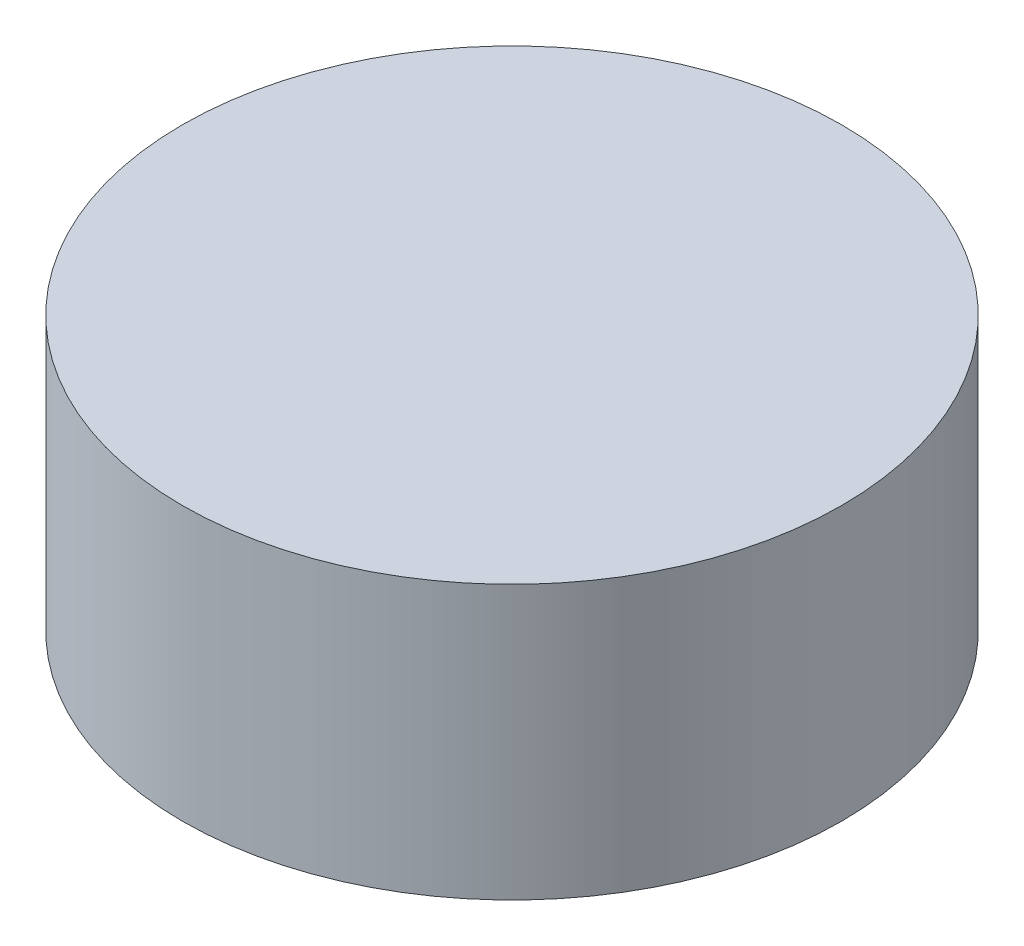
SolidWorks part; units mm, degrees
ref_plane "Front Plane" through (0, 0, 0) normal (0, 0, 1) x (1, 0, 0)
ref_plane "Top Plane" through (0, 0, 0) normal (0, 1, 0) x (1, 0, 0)
ref_plane "Right Plane" through (0, 0, 0) normal (1, 0, 0) x (0, 0, -1)
sketch "Sketch1" plane through (0, 0, 0) normal (0, 1, 0) x (1, 0, 0)
  circle A0 centre (0, 0) radius 20.5
extrude "Boss-Extrude1" add sketch "Sketch1" along normal blind 17
ref_axis "Axis1" through (0, 17, 0) along (0, -1, 0)
